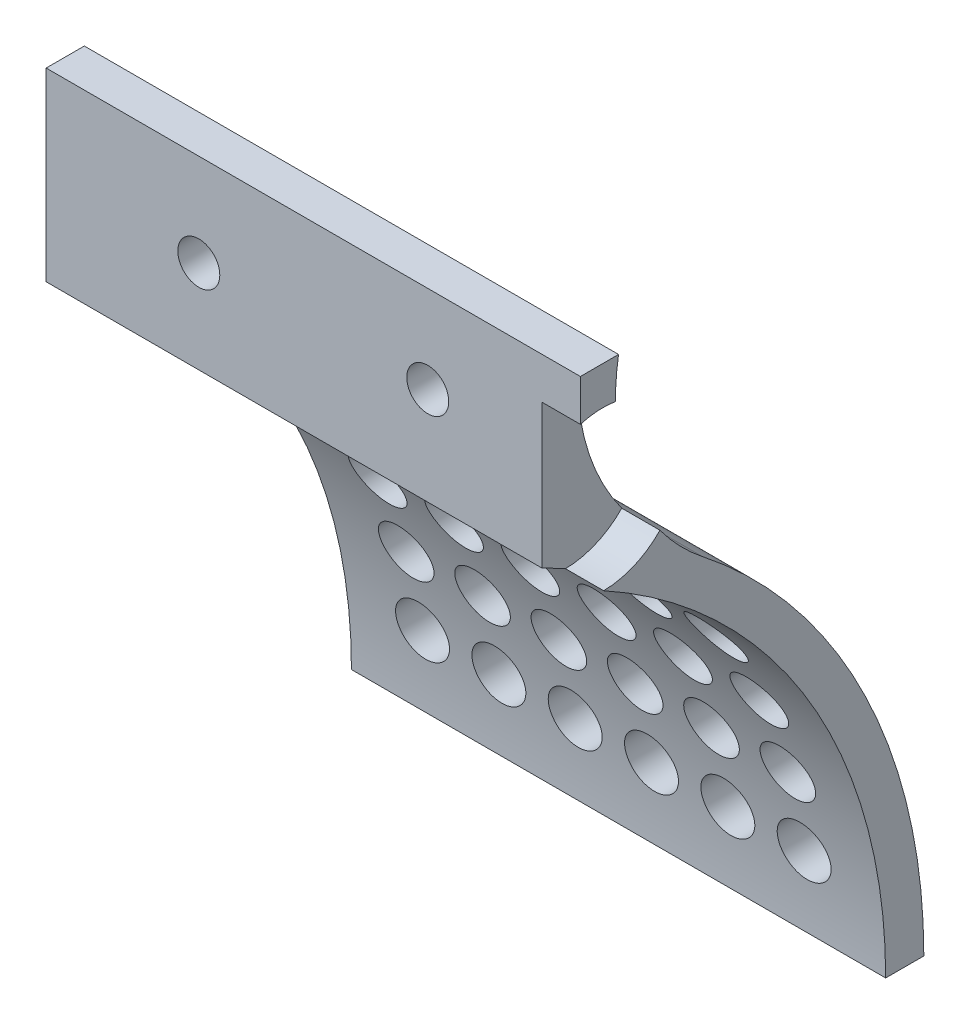
SolidWorks part; units mm, degrees
ref_plane "Alzado" through (0, 0, 0) normal (0, 0, 1) x (1, 0, 0)
ref_plane "Planta" through (0, 0, 0) normal (0, 1, 0) x (1, 0, 0)
ref_plane "Vista lateral" through (0, 0, 0) normal (1, 0, 0) x (0, 0, -1)
sketch "Croquis1" plane through (0, 0, 0) normal (1, 0, 0) x (0, 0, -1)
  line L0 (-25.1938, 53.195) -> (-20.1938, 53.195)
  line L2 (-25.1938, 53.195) -> (-25.1938, 28.9376)
  line L3 (14.8062, -35.0624) -> (19.8062, -35.0624)
  line L4 (-20.1938, 53.195) -> (-20.1938, 31.9898) construction
  arc A0 (-9.183, 24.7505) -> (19.8062, -35.0624) centre (-56.3938, -35.0624) cw
  arc A1 (-25.1938, 28.9376) -> (14.8062, -35.0624) centre (-56.3938, -35.0624) cw
  arc A2 (-20.1938, 31.9898) -> (19.8062, -35.0624) centre (-56.3938, -35.0624) cw construction
  arc A3 (-20.1938, 53.195) -> (-9.183, 24.7505) centre (9.4039, 48.2989) ccw
  dimension "D4" = 30
  dimension "D2" = 64
  dimension "D1" = 5
  dimension "D3" = 40
extrude "Saliente-Extruir1" add sketch "Croquis1" along normal blind 70
sketch "Croquis2" plane through (0, 0, 25.1938) normal (0, 0, 1) x (1, 0, 0)
  line L0 (0, 53.195) -> (0, 28.9376) construction
  line L1 (0, 53.195) -> (0, 28.9376)
  line L2 (70, 53.195) -> (70, 28.9376) construction
  circle A0 centre (20, 41.0663) radius 2.75
  circle A1 centre (50, 41.7171) radius 2.75
  point P8 (0, 41.0663)
  dimension "D1" = 5.5
  dimension "D2" = 20
  dimension "D3" = 20
ref_plane "Plano1" through (0, 0, -19.8062) normal (0, 0, 1) x (1, 0, 0)
sketch "Croquis3" plane through (0, 0, -19.8062) normal (0, 0, 1) x (1, 0, 0)
  line L0 (70, -35.0624) -> (70, 24.7505) construction
  line L1 (70, 24.7505) -> (0, 24.7505) construction
  circle A0 centre (60, 14.7505) radius 3.5
  circle A1 centre (50, 14.7505) radius 3.5
  circle A2 centre (40, 14.7505) radius 3.5
  circle A3 centre (30, 14.7505) radius 3.5
  circle A4 centre (20, 14.7505) radius 3.5
  circle A5 centre (10, 14.7505) radius 3.5
  circle A6 centre (50, 4.7505) radius 3.5
  circle A7 centre (40, 4.7505) radius 3.5
  circle A8 centre (30, 4.7505) radius 3.5
  circle A9 centre (20, 4.7505) radius 3.5
  circle A10 centre (10, 4.7505) radius 3.5
  circle A11 centre (50, -5.2495) radius 3.5
  circle A12 centre (40, -5.2495) radius 3.5
  circle A13 centre (30, -5.2495) radius 3.5
  circle A14 centre (20, -5.2495) radius 3.5
  circle A15 centre (10, -5.2495) radius 3.5
  circle A16 centre (60, 4.7505) radius 3.5
  circle A17 centre (60, -5.2495) radius 3.5
  circle A18 centre (20, -5.2495) radius 3.5
  circle A19 centre (30, -5.2495) radius 3.5
  circle A20 centre (40, -5.2495) radius 3.5
  circle A21 centre (50, -5.2495) radius 3.5
  circle A22 centre (60, -5.2495) radius 3.5
  circle A23 centre (20, -15.2495) radius 3.5
  circle A24 centre (30, -15.2495) radius 3.5
  circle A25 centre (40, -15.2495) radius 3.5
  circle A26 centre (50, -15.2495) radius 3.5
  circle A27 centre (60, -15.2495) radius 3.5
  circle A28 centre (20, -25.2495) radius 3.5
  circle A29 centre (30, -25.2495) radius 3.5
  circle A30 centre (40, -25.2495) radius 3.5
  circle A31 centre (50, -25.2495) radius 3.5
  circle A32 centre (60, -25.2495) radius 3.5
  circle A33 centre (10, -15.2495) radius 3.5
  circle A34 centre (10, -25.2495) radius 3.5
  circle A65 centre (10, 4.7505) radius 3.5
  circle A66 centre (10, -5.2495) radius 3.5
  circle A67 centre (10, -15.2495) radius 3.5
  circle A68 centre (10, -25.2495) radius 3.5
  circle A69 centre (0, 14.7505) radius 3.5 [skipped]
  circle A70 centre (-10, 14.7505) radius 3.5 [skipped]
  circle A71 centre (-20, 14.7505) radius 3.5 [skipped]
  circle A72 centre (-30, 14.7505) radius 3.5 [skipped]
  circle A73 centre (-40, 14.7505) radius 3.5 [skipped]
  circle A74 centre (-50, 14.7505) radius 3.5 [skipped]
  circle A75 centre (0, 4.7505) radius 3.5 [skipped]
  circle A76 centre (-10, 4.7505) radius 3.5 [skipped]
  circle A77 centre (-20, 4.7505) radius 3.5 [skipped]
  circle A78 centre (-30, 4.7505) radius 3.5 [skipped]
  circle A79 centre (-40, 4.7505) radius 3.5 [skipped]
  circle A80 centre (-50, 4.7505) radius 3.5 [skipped]
  circle A81 centre (0, -5.2495) radius 3.5 [skipped]
  circle A82 centre (-10, -5.2495) radius 3.5 [skipped]
  circle A83 centre (-20, -5.2495) radius 3.5 [skipped]
  circle A84 centre (-30, -5.2495) radius 3.5 [skipped]
  circle A85 centre (-40, -5.2495) radius 3.5 [skipped]
  circle A86 centre (-50, -5.2495) radius 3.5 [skipped]
  circle A87 centre (0, -15.2495) radius 3.5 [skipped]
  circle A88 centre (-10, -15.2495) radius 3.5 [skipped]
  circle A89 centre (-20, -15.2495) radius 3.5 [skipped]
  circle A90 centre (-30, -15.2495) radius 3.5 [skipped]
  circle A91 centre (-40, -15.2495) radius 3.5 [skipped]
  circle A92 centre (-50, -15.2495) radius 3.5 [skipped]
  circle A93 centre (0, -25.2495) radius 3.5 [skipped]
  circle A94 centre (-10, -25.2495) radius 3.5 [skipped]
  circle A95 centre (-20, -25.2495) radius 3.5 [skipped]
  circle A96 centre (-30, -25.2495) radius 3.5 [skipped]
  circle A97 centre (-40, -25.2495) radius 3.5 [skipped]
  circle A98 centre (-50, -25.2495) radius 3.5 [skipped]
  dimension "D1" = 7
  dimension "D2" = 10
  dimension "D3" = 10
  dimension "D4" = 6
  dimension "D5" = 3
  dimension "D6" = 6
  dimension "D7" = 3
  dimension "D8" = 7
  dimension "D9" = 5
extrude "Cortar-Extruir3" cut sketch "Croquis3" along normal blind 65 contours A0 | A1 | A2 | A3 | A4 | A5 | A16 | A6 | A17 | A11 | A12 | A7 | A8 | A9 | A13 | A14 | A15 | A10 | A23 | A33 | A34 | A28 | A24 | A25 | A30 | A29 | A26 | A31 | A27 | A32 region at (60, 14.7505, -19.8062) region at (50, 14.7505, -19.8062) region at (40, 14.7505, -19.8062) region at (30, 14.7505, -19.8062) region at (20, 14.7505, -19.8062) region at (10, 14.7505, -19.8062) region at (50, 4.7505, -19.8062) region at (40, 4.7505, -19.8062) region at (30, 4.7505, -19.8062) region at (20, 4.7505, -19.8062) region at (10, 4.7505, -19.8062) region at (50, -5.2495, -19.8062) region at (40, -5.2495, -19.8062) region at (30, -5.2495, -19.8062) region at (20, -5.2495, -19.8062) region at (10, -5.2495, -19.8062) region at (60, 4.7505, -19.8062) region at (60, -5.2495, -19.8062) region at (20, -15.2495, -19.8062) region at (30, -15.2495, -19.8062) region at (40, -15.2495, -19.8062) region at (50, -15.2495, -19.8062) region at (60, -15.2495, -19.8062) region at (20, -25.2495, -19.8062) region at (30, -25.2495, -19.8062) region at (40, -25.2495, -19.8062) region at (50, -25.2495, -19.8062) region at (60, -25.2495, -19.8062) region at (10, -15.2495, -19.8062) region at (10, -25.2495, -19.8062)
extrude "Cortar-Extruir4" cut sketch "Croquis2" against normal blind 65 contours A0 | A1 region at (20, 41.0663, 25.1938)
sketch "Croquis4" plane through (70, 0, 0) normal (1, 0, 0) x (0, 0, -1)
  circle A0 centre (-22.259, 37.7714) radius 10.4135
extrude "Cortar-Extruir5" cut sketch "Croquis4" against normal blind 5
